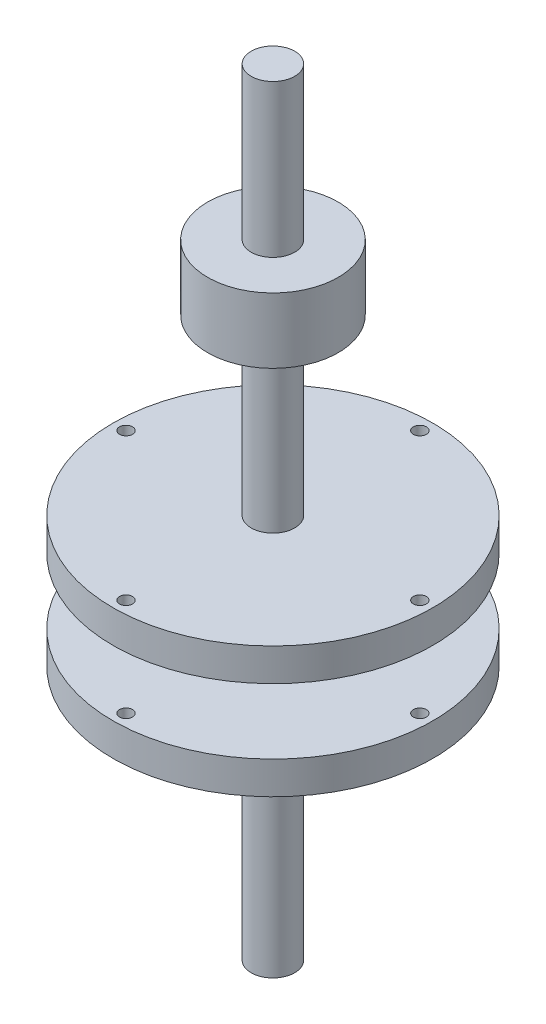
SolidWorks part; units mm, degrees
ref_plane "Front Plane" through (0, 0, 0) normal (0, 0, 1) x (1, 0, 0)
ref_plane "Top Plane" through (0, 0, 0) normal (0, 1, 0) x (1, 0, 0)
ref_plane "Right Plane" through (0, 0, 0) normal (1, 0, 0) x (0, 0, -1)
sketch "Sketch1" plane through (0, 0, 0) normal (0, 0, 1) x (1, 0, 0)
  line L0 (0, 223.9568) -> (0, -251.1973) construction
  line L1 (-10, -178.3547) -> (10, -178.3547)
  line L2 (-10, -178.3547) -> (-10, 178.3547)
  line L3 (-10, 178.3547) -> (10, 178.3547)
  line L4 (10, -178.3547) -> (10, -61.3547)
  line L5 (-10, -178.3547) -> (10, 178.3547) construction
  line L6 (-10, 178.3547) -> (10, -178.3547) construction
  line L7 (-30, 108.3548) -> (30, 108.3548)
  line L8 (-30, 108.3548) -> (-30, 78.3547)
  line L9 (-30, 78.3547) -> (30, 78.3547)
  line L10 (30, 108.3548) -> (30, 78.3547)
  line L11 (-30, 108.3548) -> (30, 78.3547) construction
  line L12 (-30, 78.3547) -> (30, 108.3548) construction
  line L13 (10, -46.3547) -> (10, -16.3547)
  line L17 (73.5, -1.3547) -> (73.5, -16.3547)
  line L18 (0, 178.3547) -> (0, -178.3547)
  line L20 (73.5, -16.3547) -> (10, -16.3547)
  line L22 (73.5, -46.3547) -> (10, -46.3547)
  line L23 (10, -16.3547) -> (10, -46.3547)
  line L24 (73.5, -46.3547) -> (73.5, -61.3547)
  line L25 (10, -1.3547) -> (10, 178.3547)
  line L26 (10, -1.3547) -> (73.5, -1.3547)
  line L27 (10, -61.3547) -> (73.5, -61.3547)
  point P0 (0, 0)
  point P6 (0, 93.3548)
  dimension "D1" = 20
  dimension "D2" = 30
  dimension "D3" = 60
  dimension "D4" = 100
  dimension "D5" = 256.7095
  dimension "D7" = 60
  dimension "D8" = 73.5
  dimension "D10" = 30
  dimension "D9" = 15
  dimension "D6" = 79.7095
revolve "Revolve3" add sketch "Sketch1" angle 360 about L0 region at (2.6702, -50, 0) region at (5, 93.3548, 0) region at (20, 93.3547, 0) region at (5, 143.3547, 0)
sketch "Sketch2" plane through (0, -61.3547, 0) normal (0, -1, 0) x (1, 0, 0)
  line L1 (-67.5, 67.5) -> (67.5, 67.5) construction
  line L2 (-67.5, 67.5) -> (-67.5, -67.5) construction
  line L3 (-67.5, -67.5) -> (67.5, -67.5) construction
  line L4 (67.5, 67.5) -> (67.5, -67.5) construction
  line L5 (-67.5, 67.5) -> (67.5, -67.5) construction
  line L6 (-67.5, -67.5) -> (67.5, 67.5) construction
  circle A0 centre (67.5, 0) radius 3
  circle A1 centre (-67.5, 0) radius 3
  circle A2 centre (0, 67.5) radius 3
  circle A3 centre (0, -67.5) radius 3
  point P0 (0, 0)
  dimension "D2" = 6
  dimension "D1" = 135
extrude "Cut-Extrude1" cut sketch "Sketch2" against normal blind 80
equation "\"hatchHoleDiameter\"= 600mm"
equation "\"hullThickness\"= 120mm"
equation "\"gasketHullInterconnectWidth\"= 100mm"
equation "\"collarThickness\"= 20mm"
equation "\"hatchTunnelLength\"=200"
equation "\"oRingDiameter\"=2"
equation "\"boltPatternRadiusInterconnect\"=500"
equation "\"interconnectBoltDiameter\"=30"
equation "\"hatchShaftDiameter\"=20"
equation "\"hatchMinima\"=50"
equation "\"hullDiameter\"=2000"
equation "\"hatchMaxima\"=180"
equation "\"bushingFlatHatch\"=15"
equation "\"hingePivotDiameter\"=20"
equation "\"handleWidth\"=250"
equation "\"handleHeight\"=160"
equation "\"handleThickness\"=25"
equation "\"FrameLength\"= 2600"
equation "\"FrameMidLength\"= 1800"
equation "\"TubeOD\"= 100"
equation "\"FrameBackFlat\"= 500"
equation "\"TubeWall\"=15"
equation "\"TopMemberAngle\"=140"
equation "\"D1@Sketch1\"=\"hatchShaftDiameter\""
equation "\"HatchShaftSeatThickness\"= 30"
equation "\"D2@Sketch1\"=\"HatchShaftSeatThickness\""
equation "\"D3@Sketch1\"=\"hatchShaftDiameter\"*3"
equation "\"D5@Sketch1\"=\"hatchEdgeToTop\"+\"hatchMaxima\""
equation "\"hatchTopToDogArmCenter\"=33mm"
equation "\"dogArmSize\"=30"
equation "\"hatchPivotHeight\"=40"
equation "\"hatchPivotDistance\"=70"
equation "\"HatchORingDiameter\"=2.1"
equation "\"hatchThickness\"=50"
equation "\"hatchEdgeToTop\"=76.7095"
equation "\"D7@Sketch1\"=\"dogArmSize\"*2"
equation "\"D9@Sketch1\"=\"dogArmSize\"/2"
equation "\"D6@Sketch1\"=\"hatchTopToDogArmCenter\"+\"hatchEdgeToTop\"-\"dogArmSize\""
equation "\"D1@Sketch2\"=67.5*2"
